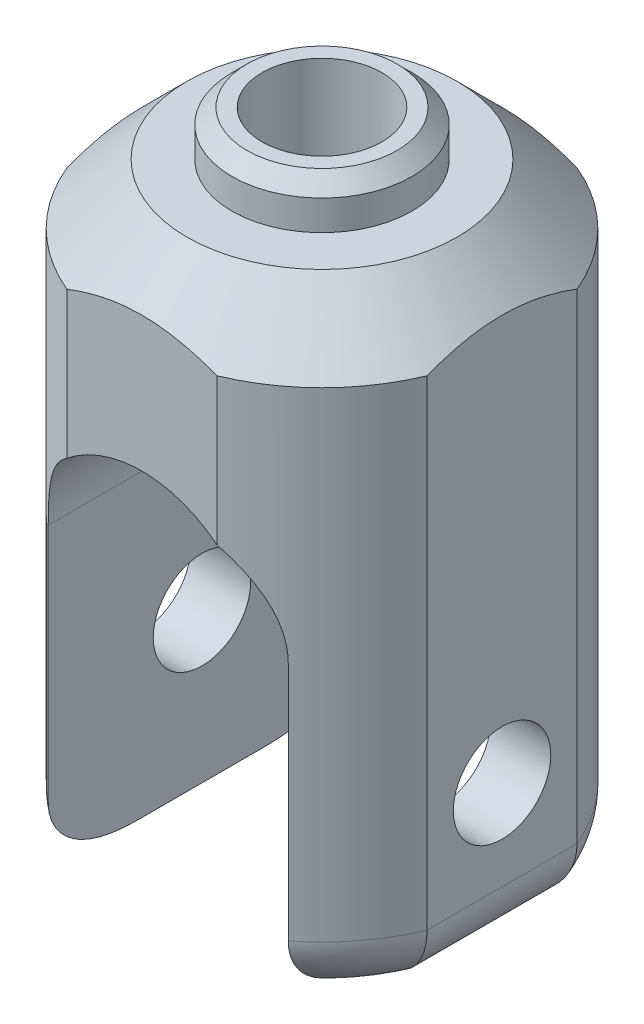
SolidWorks part; units mm, degrees
ref_plane "Front Plane" through (0, 0, 0) normal (0, 0, 1) x (1, 0, 0)
ref_plane "Top Plane" through (0, 0, 0) normal (0, 1, 0) x (1, 0, 0)
ref_plane "Right Plane" through (0, 0, 0) normal (1, 0, 0) x (0, 0, -1)
sketch "Sketch1" plane through (0, 0, 0) normal (0, 1, 0) x (1, 0, 0)
  circle A0 centre (0, 0) radius 13
  dimension "D1" = 26
extrude "Boss-Extrude1" add sketch "Sketch1" along normal blind 40
chamfer "Chamfer1" distance 4 1 edges at (0, 40, 13)
sketch "Sketch2" plane through (0, 0, 0) normal (1, 0, 0) x (0, 0, -1)
  line L0 (0, 14.3) -> (0, -14.3) construction
  line L1 (-21.2458, -4.3547) -> (-12, -4.3547)
  line L2 (-21.2458, -4.3547) -> (-21.2458, 44.6704)
  line L3 (-21.2458, 44.6704) -> (-12, 44.6704)
  line L4 (-12, -4.3547) -> (-12, 44.6704)
  line L5 (12, -4.3547) -> (12, 44.6704)
  line L6 (21.2458, 44.6704) -> (12, 44.6704)
  line L7 (21.2458, -4.3547) -> (21.2458, 44.6704)
  line L8 (21.2458, -4.3547) -> (12, -4.3547)
  dimension "D1" = 12
extrude "Cut-Extrude1" cut sketch "Sketch2" against normal mid plane 40
sketch "Sketch3" plane through (0, 0, 0) normal (0, 0, 1) x (1, 0, 0)
  line L0 (0, -23.3704) -> (0, 23.3704) construction
  line L1 (21.2866, 42.7664) -> (12, 42.7664)
  line L2 (21.2866, 42.7664) -> (21.2866, -9.4156)
  line L3 (21.2866, -9.4156) -> (12, -9.4156)
  line L4 (12, 42.7664) -> (12, -9.4156)
  line L5 (-12, 42.7664) -> (-12, -9.4156)
  line L6 (-21.2866, -9.4156) -> (-12, -9.4156)
  line L7 (-21.2866, 42.7664) -> (-21.2866, -9.4156)
  line L8 (-21.2866, 42.7664) -> (-12, 42.7664)
  dimension "D1" = 12
extrude "Cut-Extrude2" cut sketch "Sketch3" against normal mid plane 40
sketch "Sketch4" plane through (0, 0, 0) normal (0, 0, 1) x (1, 0, 0)
  line L0 (9, 40) -> (-9, 40) construction
  line L1 (8, 20) -> (8, 0)
  line L2 (5, 0) -> (12, 0) construction
  line L3 (8, 0) -> (-8, 0)
  line L4 (-12, 0) -> (-5, 0) construction
  line L5 (-8, 0) -> (-8, 20)
  arc A0 (8, 20) -> (-8, 20) centre (0, 20) ccw
  dimension "D1" = 16
  dimension "D2" = 20
extrude "Cut-Extrude3" cut sketch "Sketch4" against normal mid plane 40
fillet "Fillet9" radius 4 6 edges at (12, 0, 0) (10.3384, 0, 7.8815) (10.3384, 0, -7.8815) (-10.3384, 0, 7.8815) (-12, 0, 0) (-10.3384, 0, -7.8815)
sketch "Sketch5" plane through (12, 0, 0) normal (1, 0, 0) x (0, 0, -1)
  line L0 (9, 40) -> (-9, 40) construction
  circle A0 centre (0, 10) radius 3.25
  dimension "D1" = 6.5
  dimension "D2" = 30
extrude "Cut-Extrude4" cut sketch "Sketch5" against normal up to surface (24 mm away) up to face at (-12, 20.248, 0.1095)
sketch "Sketch6" plane through (0, 40, 0) normal (0, 1, 0) x (1, 0, 0)
  circle A0 centre (0, 0) radius 6
  dimension "D1" = 12
extrude "Boss-Extrude2" add sketch "Sketch6" along normal blind 3
sketch "Sketch7" plane through (0, 43, 0) normal (0, 1, 0) x (1, 0, 0)
  circle A0 centre (0, 0) radius 4
  dimension "D1" = 8
extrude "Cut-Extrude5" cut sketch "Sketch7" against normal up to surface (15 mm away) up to face at (0, 23.6281, 0)
chamfer "Chamfer2" distance 1 1 edges at (0, 43, 6)
